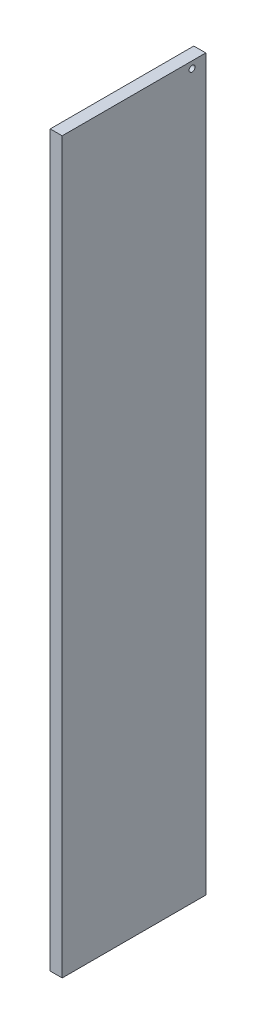
SolidWorks part; units mm, degrees
material "6061 Alloy"
ref_plane "Front Plane" through (0, 0, 0) normal (0, 0, 1) x (1, 0, 0)
ref_plane "Top Plane" through (0, 0, 0) normal (0, 1, 0) x (1, 0, 0)
ref_plane "Right Plane" through (0, 0, 0) normal (1, 0, 0) x (0, 0, -1)
sketch "Sketch1" plane through (0, 0, 0) normal (1, 0, 0) x (0, 0, -1)
  line L1 (-38.1, 193.548) -> (38.1, 193.548)
  line L2 (-38.1, 193.548) -> (-38.1, -193.548)
  line L3 (-38.1, -193.548) -> (38.1, -193.548)
  line L4 (38.1, 193.548) -> (38.1, -193.548)
  line L5 (-38.1, 193.548) -> (38.1, -193.548) construction
  line L6 (-38.1, -193.548) -> (38.1, 193.548) construction
  point P0 (0, 0)
  dimension "D1" = 387.096
  dimension "D2" = 76.2
extrude "Boss-Extrude1" add sketch "Sketch1" along normal blind 6.35
sketch "Sketch2" plane through (6.35, 0, 0) normal (1, 0, 0) x (0, 0, -1)
  circle A0 centre (30.8167, 189.9293) radius 1.5875
extrude "Cut-Extrude1" cut sketch "Sketch2" against normal up to next
